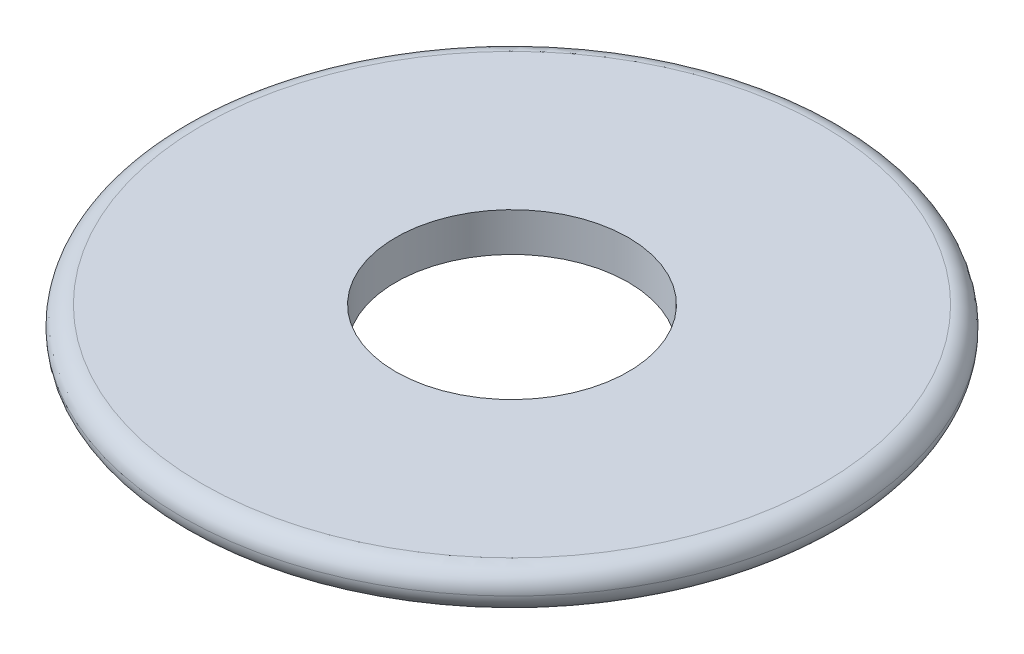
SolidWorks part; units mm, degrees
ref_plane "Plano frontal" through (0, 0, 0) normal (0, 0, 1) x (1, 0, 0)
ref_plane "Plano superior" through (0, 0, 0) normal (0, 1, 0) x (1, 0, 0)
ref_plane "Plano direito" through (0, 0, 0) normal (1, 0, 0) x (0, 0, -1)
sketch "Esboço1" plane through (0, 0, 0) normal (0, 1, 0) x (1, 0, 0)
  circle A0 centre (0, 0) radius 3
  circle A1 centre (0, 0) radius 8.5
  dimension "D1" = 6
  dimension "D2" = 17
extrude "Ressalto-extrusão1" add sketch "Esboço1" along normal blind 1
fillet "Filete1" radius 0.5 2 edges at (0, 0, 8.5) (0, 1, 8.5)
